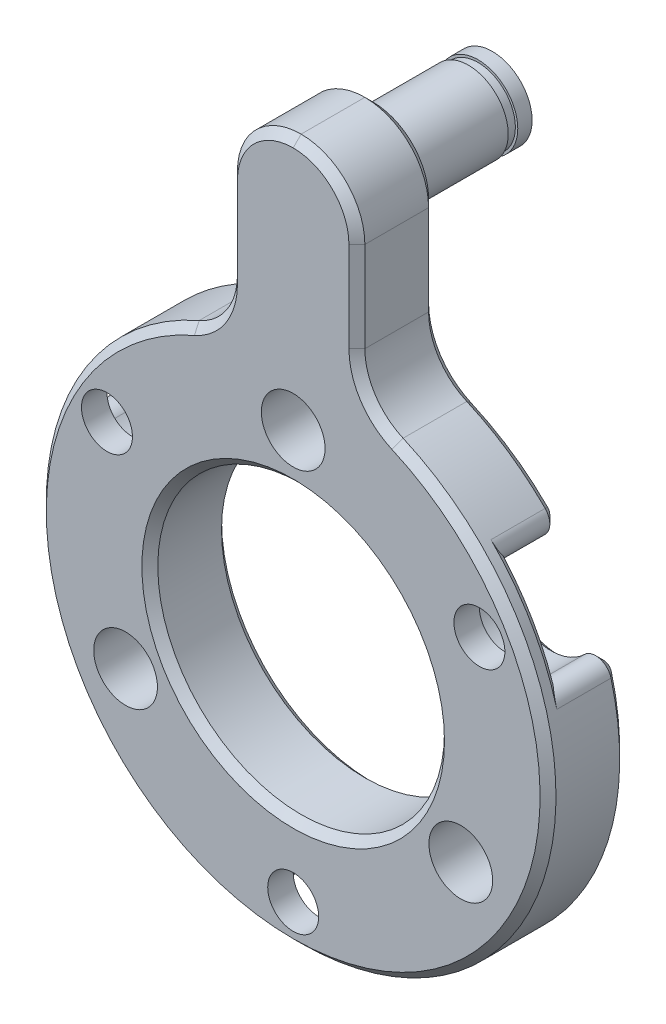
SolidWorks part; units mm, degrees
material "1.0503 (C45)"
ref_plane "前视基准面" through (0, 0, 0) normal (0, 0, 1) x (1, 0, 0)
ref_plane "上视基准面" through (0, 0, 0) normal (0, 1, 0) x (1, 0, 0)
ref_plane "右视基准面" through (0, 0, 0) normal (1, 0, 0) x (0, 0, -1)
other "Configuration Table"
sketch "草图1" plane through (0, 0, 0) normal (0, 0, 1) x (1, 0, 0)
  circle A0 centre (0, 0) radius 16
  dimension "D1" = 32
extrude "凸台-拉伸1" add sketch "草图1" along normal mid plane 5
hole_wizard "Ø4.0mm 暗销孔1" positions "草图2" profile "草图3" hole size "Ø4.0" standard "GB"
sketch "草图2" plane through (0, 0, 2.5) normal (0, 0, 1) x (1, 0, 0)
  circle A0 centre (0, 0) radius 12.15
  point P0 (0, 12.15)
  point P15 (10.5222, -6.075)
  point P16 (-10.5222, -6.075)
  dimension "D1" = 24.3
  dimension "D2" = 3
sketch "草图3" plane through (0, 12.15, 2.5) normal (1, 0, 0) x (0, -1, 0)
  line L0 (0, 0) -> (0, 4.2017)
  line L1 (0, 4.2017) -> (2, 3)
  line L2 (2, 3) -> (2, 0)
  line L5 (2, 0) -> (0, 0)
  line L10 (0, 4.2017) -> (-2, 3) construction
  line L11 (0, -6.35) -> (0, 107.95) construction
  dimension "孔直径" = 4
  dimension "孔深度" = 3
  dimension "导头角度" = 118
hole_wizard "M3 六角圆柱头螺钉的柱形沉头孔1" positions "草图4" profile "草图5" counterbore size "M3" standard "GB" end condition up to next
sketch "草图4" plane through (0, 0, -2.5) normal (0, 0, -1) x (-1, 0, 0)
  circle A0 centre (0, 0) radius 13.5
  point P0 (0, -13.5)
  point P14 (-11.6913, 6.75)
  point P15 (11.6913, 6.75)
  dimension "D1" = 27
  dimension "D2" = 3
sketch "草图5" plane through (0, -13.5, -2.5) normal (1, 0, 0) x (0, 1, 0)
  line L0 (0, 0) -> (0, 5)
  line L1 (0, 5) -> (1.6, 5)
  line L3 (1.6, 5) -> (1.6, 3.4)
  line L4 (1.6, 3.4) -> (3, 3.4)
  line L5 (3, 3.4) -> (3, 0)
  line L7 (3, 0) -> (0, 0)
  line L11 (0, -6.35) -> (0, 107.95) construction
  dimension "通孔孔直径" = 3.2
  dimension "通孔孔深度" = 5
  dimension "柱形沉头孔直径" = 6
  dimension "柱形沉头孔深度" = 3.4
fillet "圆角1" radius 1 6 edges at (14.6694, 6.3881, -0.8) (12.867, 9.5101, -0.8) (-14.6694, 6.3881, -0.8) (-12.867, 9.5101, -0.8) (1.8025, -15.8981, -0.8) (-1.8025, -15.8981, -0.8)
sketch "草图6" plane through (0, 0, -2.5) normal (0, 0, -1) x (-1, 0, 0)
  circle A0 centre (0, 24) radius 2.5
  dimension "D1" = 5
  dimension "D2" = 24
extrude "凸台-拉伸2" add sketch "草图6" along normal blind 7.5
sketch "草图9" plane through (0, 0, -2.5) normal (0, 0, -1) x (-1, 0, 0)
  line L0 (0, 30.4507) -> (0, -2.4734) construction
  line L1 (-4, 15.4919) -> (-4, 28)
  line L2 (-4, 28) -> (4, 28)
  line L3 (4, 28) -> (4, 15.4919)
  arc A2 (11.3191, 11.3083) -> (-11.3191, 11.3083) centre (0, 0) ccw construction
  arc A4 (4, 15.4919) -> (-4, 15.4919) centre (0, 0) ccw
  circle A6 centre (0, 24) radius 2.5
  circle A7 centre (0, 24) radius 2.5 construction
  dimension "D1" = 0
  dimension "D2" = 8
  dimension "D3" = 4
extrude "凸台-拉伸3" add sketch "草图9" against normal up to surface (5 mm away) up to face at (1.6, -13.5, 2.5)
sketch "草图7" plane through (0, 0, -2.5) normal (0, 0, -1) x (-1, 0, 0)
  circle A0 centre (0, 0) radius 9
  dimension "D1" = 18
extrude "切除-拉伸1" cut sketch "草图7" against normal through all
ref_plane "基准面1" through (0, 0, -8.5) normal (0, 0, -1) x (-1, 0, 0)
sketch "草图8" plane through (0, 0, -8.5) normal (0, 0, -1) x (-1, 0, 0)
  circle A0 centre (0, 24) radius 2.35
  circle A2 centre (0, 24) radius 2.5
  circle A3 centre (0, 24) radius 2.5
  dimension "D1" = 4.7
  dimension "D2" = 0
extrude "切除-拉伸2" cut sketch "草图8" along normal blind 0.6
fillet "圆角3" radius 4 4 edges at (4, 28, 0) (-4, 28, 0) (-4, 15.4919, 0) (4, 15.4919, 0)
chamfer "倒角1" distance 0.5 angle 45 31 edges at (-9, 0, -2.5) (-9, 0, 2.5) (0, -16, 0.9) (13.8564, 8, 0.9) (-13.8564, 8, 0.9) (0, -16, 2.5) (9.0933, 5.25, -2.5) (11.579, 10.348, -2.5) (14.7512, 4.8537, -2.5) (9.0171, 13.2171, -2.5) (13.8564, -8, -2.5) (3.1722, -15.2017, -2.5) (0, -10.5, -2.5) (-3.1722, -15.2017, -2.5) (-9.0171, 13.2171, -2.5) (-13.8564, -8, -2.5) (-11.579, 10.348, -2.5) (-14.7512, 4.8537, -2.5) (-9.0933, 5.25, -2.5) (-2.8284, 26.8284, 2.5) (2.8284, 26.8284, 2.5) (-4, 21.1652, 2.5) (4, 21.1652, 2.5) (-4.6534, 16.1394, 2.5) (4.6534, 16.1394, 2.5) (4.6534, 16.1394, -2.5) (4, 21.1652, -2.5) (2.8284, 26.8284, -2.5) (-2.8284, 26.8284, -2.5) (-4, 21.1652, -2.5) (-4.6534, 16.1394, -2.5)
